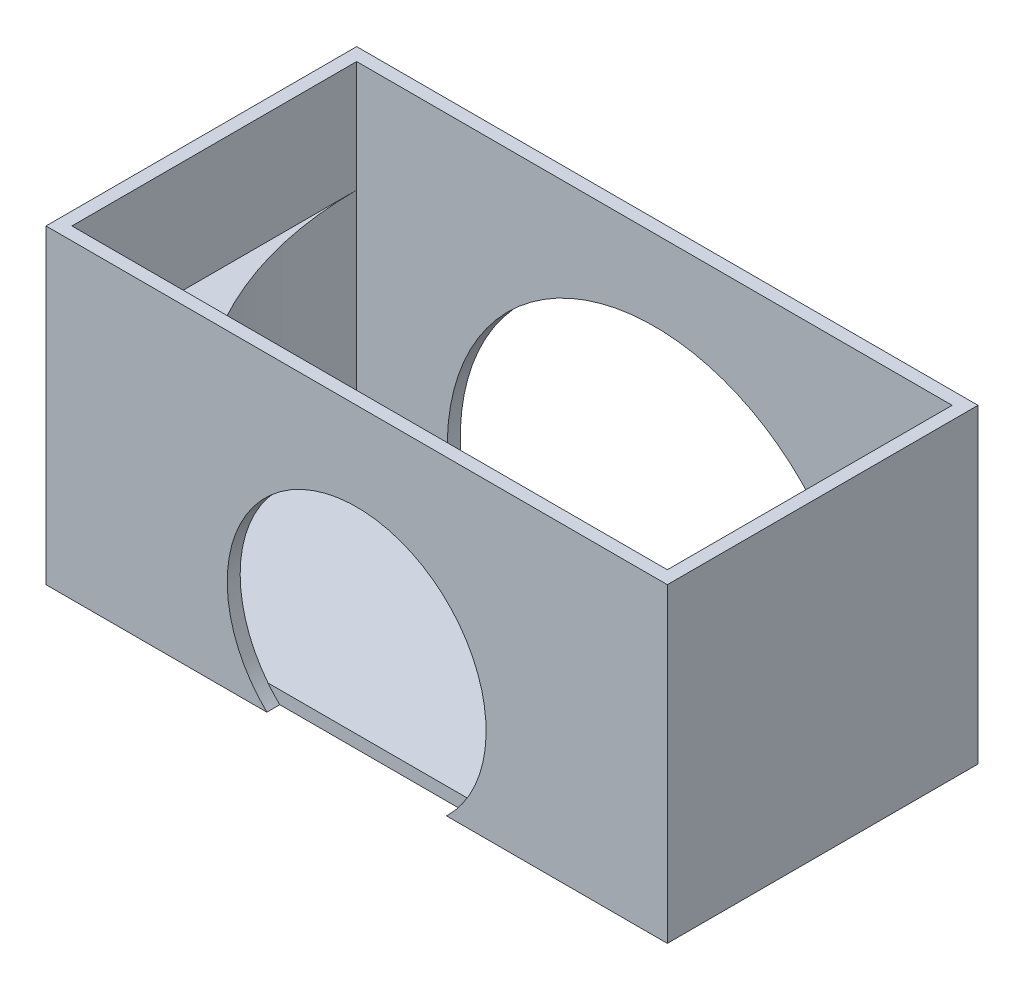
SolidWorks part; units mm, degrees
ref_plane "Front Plane" through (0, 0, 0) normal (0, 0, 1) x (1, 0, 0)
ref_plane "Top Plane" through (0, 0, 0) normal (0, 1, 0) x (1, 0, 0)
ref_plane "Right Plane" through (0, 0, 0) normal (1, 0, 0) x (0, 0, -1)
sketch "Sketch1" plane through (0, 0, 0) normal (0, 1, 0) x (1, 0, 0)
  line L1 (76.2, -38.1) -> (-76.2, -38.1)
  line L2 (76.2, -38.1) -> (76.2, 38.1)
  line L3 (76.2, 38.1) -> (-76.2, 38.1)
  line L4 (-76.2, -38.1) -> (-76.2, 38.1)
  line L5 (76.2, -38.1) -> (-76.2, 38.1) construction
  line L6 (76.2, 38.1) -> (-76.2, -38.1) construction
  point P0 (0, 0)
  dimension "D1" = 152.4
  dimension "D2" = 76.2
extrude "Boss-Extrude1" add sketch "Sketch1" along normal blind 76.2
shell "Shell1" thickness 3.175 removed face at (0, 76.2, 0)
sketch "Sketch2" plane through (0, 0, -38.1) normal (0, 0, -1) x (-1, 0, 0)
  line L1 (-76.2, 0) -> (76.2, 0) construction
  line L2 (-50.4822, 0) -> (50.4822, 0)
  arc A0 (-50.4822, 0) -> (50.4822, 0) centre (0, 5.6735) cw
  point P3 (0, 56.4735)
  dimension "D1" = 50.8
  dimension "D2" = 50.4822
  dimension "D3" = 0
extrude "Cut-Extrude1 BACK MOUSEHOLE" cut sketch "Sketch2" against normal up to surface (3.175 mm away) up to face at (0, 39.6875, -34.925)
sketch "Sketch3" plane through (0, 0, 38.1) normal (0, 0, 1) x (1, 0, 0)
  circle A0 centre (0, 22.86) radius 31.75
  dimension "D1" = 63.5
  dimension "D2" = 22.86
extrude "Cut-Extrude2" cut sketch "Sketch3" against normal up to surface (3.175 mm away) up to face at (0, 39.6875, 34.925)
sketch "Sketch4" plane through (0, 3.175, 0) normal (0, 1, 0) x (1, 0, 0)
  line L0 (-73.025, 34.925) -> (-73.025, -34.925)
  line L1 (-73.025, -34.925) -> (-39.5001, -34.925)
  line L2 (-73.025, -34.925) -> (73.025, -34.925) construction
  arc A0 (-73.025, 34.925) -> (-39.5001, -34.925) centre (16.5045, 34.925) ccw
extrude "Boss-Extrude2" add sketch "Sketch4" along normal blind 45.72 separate body
equation "\"eighthinch\"= 0.125"
